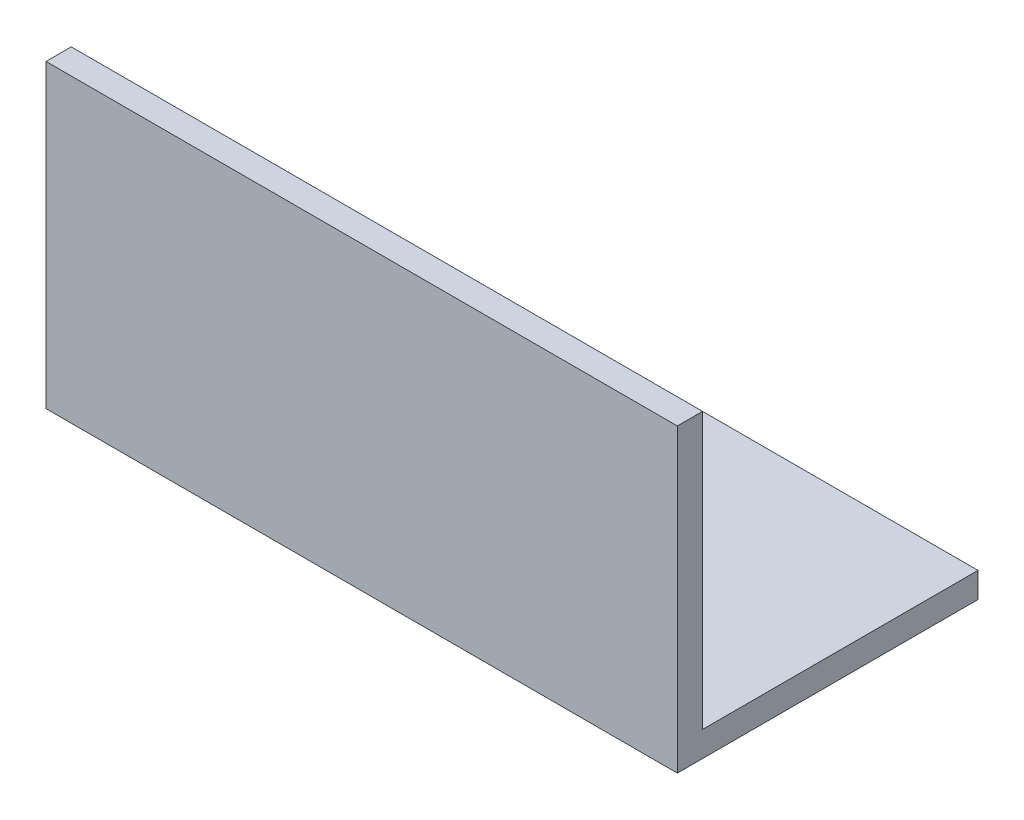
SolidWorks part; units mm, degrees
ref_plane "Front Plane" through (0, 0, 0) normal (0, 0, 1) x (1, 0, 0)
ref_plane "Top Plane" through (0, 0, 0) normal (0, 1, 0) x (1, 0, 0)
ref_plane "Right Plane" through (0, 0, 0) normal (1, 0, 0) x (0, 0, -1)
sketch "Sketch1" plane through (0, 0, 0) normal (1, 0, 0) x (0, 0, -1)
  line L0 (0, 0) -> (0, 19.05)
  line L1 (0, 19.05) -> (1.6, 19.05)
  line L2 (1.6, 19.05) -> (1.6, 1.6)
  line L3 (1.6, 1.6) -> (19.05, 1.6)
  line L4 (19.05, 1.6) -> (19.05, 0)
  line L5 (19.05, 0) -> (0, 0)
  dimension "D1" = 1.6
  dimension "D2" = 1.6
  dimension "D3" = 19.05
  dimension "D4" = 19.05
extrude "Boss-Extrude1" add sketch "Sketch1" along normal mid plane 40
